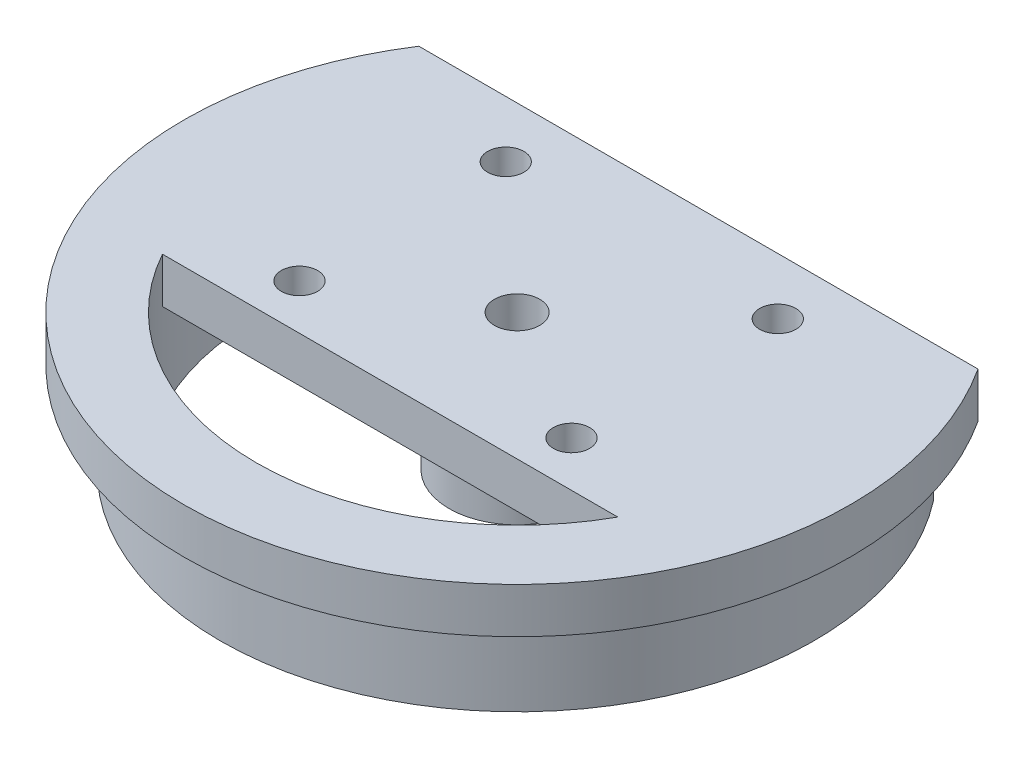
SolidWorks part; units mm, degrees
ref_plane "Спереди" through (0, 0, 0) normal (0, 0, 1) x (1, 0, 0)
ref_plane "Сверху" through (0, 0, 0) normal (0, 1, 0) x (1, 0, 0)
ref_plane "Справа" through (0, 0, 0) normal (1, 0, 0) x (0, 0, -1)
sketch "Эскиз1" plane through (0, 0, 0) normal (0, 1, 0) x (1, 0, 0)
  circle A0 centre (0, 0) radius 2.5
  circle A1 centre (0, 0) radius 7.5
  dimension "D1" = 15
  dimension "D2" = 5
extrude "cylinder" add sketch "Эскиз1" along normal blind 5 and the other way blind 10
sketch "Эскиз2" plane through (0, 0, 0) normal (0, 1, 0) x (1, 0, 0)
  circle A0 centre (0, 0) radius 36.75
  circle A1 centre (0, 0) radius 2.5
  dimension "D1" = 73.5
  dimension "D2" = 5
extrude "base horizont" add sketch "Эскиз2" along normal blind 5
sketch "Эскиз3" plane through (0, 5, 0) normal (0, 1, 0) x (1, 0, 0)
  circle A0 centre (0, 0) radius 28.75
  circle A1 centre (0, 0) radius 32.75
  dimension "D1" = 57.5
  dimension "D2" = 65.5
extrude "edge" add sketch "Эскиз3" against normal blind 15
sketch "Эскиз4" plane through (0, 5, 0) normal (0, 1, 0) x (1, 0, 0)
  line L0 (-10, 7.5) -> (10, 7.5) construction
  line L1 (-10, 2.5) -> (10, 2.5) construction
  line L2 (-10, 2.5) -> (-10, 20) construction
  line L3 (-10, 20) -> (10, 20) construction
  line L4 (10, 2.5) -> (10, 20) construction
  line L5 (-20, 20) -> (-10, 20) construction
  line L6 (10, 20) -> (20, 20) construction
  line L7 (20, 20) -> (20, 7.5) construction
  line L8 (20, 7.5) -> (-20, 7.5) construction
  line L9 (-20, 20) -> (-20, 7.5) construction
  circle A0 centre (-15, 13.75) radius 2
  circle A1 centre (0, 0) radius 2.5 construction
  circle A2 centre (15, 13.75) radius 2
  point P4 (0, 2.5)
  point P14 (-20, 13.75)
  point P19 (-15, 20)
  point P20 (15, 20)
  dimension "D6" = 4
  dimension "D1" = 20
  dimension "D2" = 20
  dimension "D3" = 12.5
  dimension "D4" = 10
  dimension "D5" = 40
sketch "Эскиз8" plane through (0, 0, 0) normal (0, 1, 0) x (1, 0, 0)
  line L1 (-30.8312, 36.75) -> (30.8312, 36.75)
  line L2 (-30.8312, 36.75) -> (-30.8312, 20)
  line L3 (-30.8312, 20) -> (30.8312, 20)
  line L4 (30.8312, 36.75) -> (30.8312, 20)
  circle A1 centre (0, 0) radius 36.75 construction
  dimension "D1" = 20
sketch "Эскиз10" plane through (0, 5, 0) normal (0, 1, 0) x (1, 0, 0)
  line L0 (0, -14) -> (45.2157, -14) construction
  line L1 (-25.111, -14) -> (25.111, -14)
  arc A0 (-25.111, -14) -> (25.111, -14) centre (0, 0) ccw
  circle A6 centre (0, 0) radius 28.75 construction
  dimension "D1" = 14
extrude "pie" cut sketch "Эскиз10" against normal up to next
sketch "Эскиз11" plane through (0, 5, 0) normal (0, 1, 0) x (1, 0, 0)
  line L0 (-10, -7.8) -> (-10, -14) construction
  line L1 (25.111, -14) -> (-25.111, -14) construction
  line L2 (-10, -14) -> (-4.1, -14) construction
  line L3 (-4.1, -14) -> (-4.1, -7.8) construction
  line L4 (-4.1, -7.8) -> (-10, -7.8) construction
  line L6 (0, 0) -> (0, -14) construction
  line L7 (4.1, -7.8) -> (10, -7.8) construction
  line L8 (4.1, -14) -> (4.1, -7.8) construction
  line L9 (10, -14) -> (4.1, -14) construction
  line L10 (10, -7.8) -> (10, -14) construction
  line L12 (-4.1, -7.8) -> (4.1, -7.8) construction
  line L13 (10, -14) -> (20, -14) construction
  line L14 (10, -14) -> (10, -4) construction
  line L15 (10, -4) -> (20, -4) construction
  line L16 (20, -14) -> (20, -4) construction
  line L17 (-10, -14) -> (-20, -14) construction
  line L18 (-10, -14) -> (-10, -4) construction
  line L19 (-10, -4) -> (-20, -4) construction
  line L20 (-20, -14) -> (-20, -4) construction
  circle A0 centre (-15, -9) radius 2
  circle A1 centre (15, -9) radius 2
  point P20 (15, -4)
  point P21 (-20, -9)
  point P22 (-15, -4)
  dimension "D6" = 4
  dimension "D1" = 6.2
  dimension "D2" = 8.2
  dimension "D3" = 20
  dimension "D4" = 10
  dimension "D5" = 10
extrude "cutoff" cut sketch "Эскиз8" against normal blind 10 and the other way blind 10
extrude "main horns holes" cut sketch "Эскиз4" against normal up to next
extrude "minor horns holes" cut sketch "Эскиз11" against normal up to next
